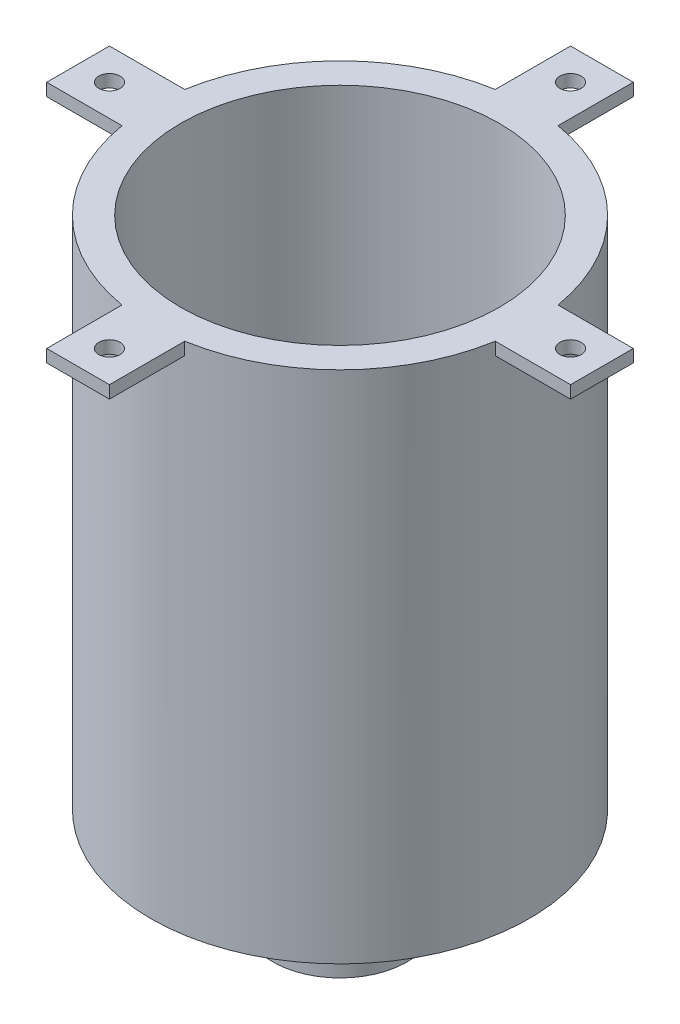
SolidWorks part; units mm, degrees
ref_plane "Front Plane" through (0, 0, 0) normal (0, 0, 1) x (1, 0, 0)
ref_plane "Top Plane" through (0, 0, 0) normal (0, 1, 0) x (1, 0, 0)
ref_plane "Right Plane" through (0, 0, 0) normal (1, 0, 0) x (0, 0, -1)
sketch "Sketch1" plane through (0, 0, 0) normal (0, 0, 1) x (1, 0, 0)
  line L0 (0, 0) -> (0, 47.7) construction
  line L1 (0, 47.7) -> (3.25, 47.7) construction
  line L2 (3.25, 47.7) -> (4.8, 47.7)
  line L3 (4.8, 47.7) -> (5.2, 43.2178)
  line L4 (5.2, 43.2178) -> (4.8, 42.5333)
  line L5 (4.8, 42.5333) -> (5.2, 38.0511)
  line L6 (5.2, 38.0511) -> (4.8, 37.3667)
  line L7 (4.8, 37.3667) -> (5.2, 32.8845)
  line L8 (5.2, 32.8845) -> (4.8, 32.2)
  line L9 (4.8, 32.2) -> (5.25, 26.2)
  line L10 (5.5, 0) -> (5.5, 18)
  line L11 (5.5, 18) -> (3.25, 19.7)
  line L12 (5.25, 26.2) -> (5.25, 22.2)
  line L13 (5.25, 22.2) -> (10.6, 22.2)
  line L14 (10.6, 22.2) -> (10.6, 15)
  line L15 (10.6, 15) -> (8.3, 15)
  line L16 (8.3, 15) -> (8.3, 0)
  line L17 (8.3, 0) -> (5.5, 0)
  line L18 (3.25, 19.7) -> (3.25, 47.7)
  dimension "D1" = 6.5
  dimension "D2" = 9.6
  dimension "D3" = 10.4
  dimension "D4" = 47.7
  dimension "D5" = 4.5
  dimension "D6" = 25.5
  dimension "D7" = 21.2
  dimension "D8" = 7.2
  dimension "D9" = 4
  dimension "D10" = 10.5
  dimension "D11" = 6
  dimension "D12" = 16.6
  dimension "D13" = 11
  dimension "D14" = 28
  dimension "D15" = 18
revolve "Revolve1" add sketch "Sketch1" angle 360 about L0
sketch "Sketch2" plane through (0, 0, 0) normal (0, 0, 1) x (1, 0, 0)
  line L0 (7.5, 0) -> (8.3, 0.4619)
  line L1 (8.3, 0) -> (5.5, 0) construction
  line L2 (8.3, 15) -> (8.3, 0) construction
  line L3 (8.3, 0.4619) -> (8.3, -0.4619)
  line L4 (8.3, -0.4619) -> (7.5, 0)
  line L5 (-7.5, 0) -> (7.5, 0) construction
  point P12 (0, 0)
  dimension "D1" = 15
sketch "Sketch3" plane through (0, 0, 0) normal (0, -1, 0) x (1, 0, 0)
  circle A0 centre (0, 0) radius 8.3 construction
  circle A1 centre (0, 0) radius 8.3
sketch "Sketch5" plane through (0, 22.2, 0) normal (0, 1, 0) x (1, 0, 0)
  line L0 (-5.3, 9.1799) -> (5.3, 9.1799)
  line L1 (5.3, 9.1799) -> (10.6, 0)
  line L2 (10.6, 0) -> (8.3, 0) construction
  line L3 (10.6, 0) -> (5.3, -9.1799)
  line L4 (5.3, -9.1799) -> (-5.3, -9.1799)
  line L5 (-5.3, -9.1799) -> (-10.6, 0)
  line L6 (-10.6, 0) -> (-5.3, 9.1799)
  circle A0 centre (0, 0) radius 10.6 construction
extrude "Cut-Extrude1" cut sketch "Sketch5" against normal up to surface (7.2 mm away) flip side to cut up to face at (0, 15, -10.6)
sketch "Sketch4" plane through (0, 0, 0) normal (0, 0, 1) x (1, 0, 0)
  line L0 (6.9, 0) -> (8.3, 1.4)
  line L1 (8.3, 0) -> (5.5, 0) construction
  line L2 (8.3, 15) -> (8.3, 0) construction
  line L3 (8.3, 1.4) -> (8.3, 0)
  line L4 (8.3, 0) -> (6.9, 0)
  line L5 (0, 0) -> (0, 15) construction
  line L6 (0, 0) -> (0, 47.7) construction
  line L7 (-8.3, 15) -> (8.3, 15) construction
  line L8 (0, 15) -> (8.3, 15) construction
  line L10 (8.3, 15) -> (10.6, 15.8371)
  line L11 (10.6, 22.2) -> (10.6, 15) construction
  line L12 (10.6, 15.8371) -> (10.6, 15)
  line L13 (10.6, 15) -> (8.3, 15)
  line L14 (8.3, 15) -> (8.3, 22.2) construction
  line L15 (5.25, 22.2) -> (10.6, 22.2) construction
  line L16 (8.3, 22.2) -> (10.6, 21.3629)
  line L17 (10.6, 21.3629) -> (10.6, 22.2)
  line L18 (10.6, 22.2) -> (8.3, 22.2)
  dimension "D1" = 45
  dimension "D2" = 20
revolve "Cut-Revolve1" cut sketch "Sketch4" angle 360 about L5
sketch "Sketch10" plane through (0, 0, 0) normal (0, -1, 0) x (1, 0, 0)
  circle A0 centre (0, 0) radius 10.705
  circle A3 centre (0, 0) radius 6.9 construction
  circle A4 centre (0, 0) radius 6.9
  dimension "D1" = 21.41
extrude "Boss-Extrude1" add sketch "Sketch10" against normal up to surface (15.8753 mm away) up to face at (0, 15.8371, 0)
sketch "Sketch11" plane through (0, 0, 0) normal (0, -1, 0) x (1, 0, 0)
  circle A0 centre (0, 0) radius 7.874
  circle A1 centre (0, 0) radius 5.5 construction
  circle A2 centre (0, 0) radius 5.5
  dimension "D1" = 15.748
extrude "Cut-Extrude2" cut sketch "Sketch11" against normal up to surface (16.2063 mm away) up to face at (0, 18, -5.5)
sketch "Sketch12" plane through (0, 22.2, 0) normal (0, 1, 0) x (1, 0, 0)
  line L0 (-7.6094, 13.1799) -> (-15.2188, 0)
  line L1 (-15.2188, 0) -> (-7.6094, -13.1799)
  line L2 (-7.6094, -13.1799) -> (7.6094, -13.1799)
  line L3 (7.6094, -13.1799) -> (15.2188, 0)
  line L4 (15.2188, 0) -> (7.6094, 13.1799)
  line L5 (7.6094, 13.1799) -> (-7.6094, 13.1799)
  line L6 (-5.3, 9.1799) -> (-10.6, 0)
  line L7 (-10.6, 0) -> (-5.3, -9.1799)
  line L8 (-5.3, -9.1799) -> (5.3, -9.1799)
  line L9 (5.3, -9.1799) -> (10.6, 0)
  line L10 (10.6, 0) -> (5.3, 9.1799)
  line L11 (5.3, 9.1799) -> (-5.3, 9.1799)
  line L12 (-5.3, 9.1799) -> (-10.6, 0) construction
  line L13 (-10.6, 0) -> (-5.3, -9.1799) construction
  line L14 (-5.3, -9.1799) -> (5.3, -9.1799) construction
  line L15 (5.3, -9.1799) -> (10.6, 0) construction
  line L16 (10.6, 0) -> (5.3, 9.1799) construction
  line L17 (5.3, 9.1799) -> (-5.3, 9.1799) construction
  circle A0 centre (0, 0) radius 8.3 construction
  circle A1 centre (0, 0) radius 8.3
  dimension "D1" = 0
  dimension "D2" = 4
extrude "Boss-Extrude3" add sketch "Sketch12" against normal up to surface (4.6818 mm away) up to face at (0, 15.8371, 0)
sketch "Sketch13" plane through (0, 47.7, 0) normal (0, 1, 0) x (1, 0, 0)
  circle A0 centre (0, 0) radius 3.45
  circle A1 centre (0, 0) radius 3.25 construction
  dimension "D1" = 0.2
extrude "Cut-Extrude3" cut sketch "Sketch13" against normal up to surface (28.1511 mm away)
sketch "Sketch14" plane through (0, 47.7, 0) normal (0, 1, 0) x (1, 0, 0)
  circle A0 centre (0, 0) radius 23.9795
extrude "Cut-Extrude5" cut sketch "Sketch14" against normal blind 32
sketch "Sketch16" plane through (0, 15.7, 0) normal (0, 1, 0) x (1, 0, 0)
  circle A0 centre (0, 0) radius 30.1625
  circle A1 centre (0, 0) radius 7.874 construction
  circle A2 centre (0, 0) radius 7.874
  dimension "D1" = 60.325
extrude "Boss-Extrude4" add sketch "Sketch16" along normal blind 2
sketch "Sketch17" plane through (0, 17.7, 0) normal (0, 1, 0) x (1, 0, 0)
  circle A0 centre (0, 0) radius 25.4
  circle A1 centre (0, 0) radius 30.1625
  circle A2 centre (0, 0) radius 30.1625
  dimension "D2" = 50.8
  dimension "D1" = 0
extrude "Boss-Extrude5" add sketch "Sketch17" along normal blind 80
sketch "Sketch18" plane through (0, 97.7, 0) normal (0, 1, 0) x (1, 0, 0)
  line L0 (-30.1625, 0) -> (0, 0) construction
  line L1 (0, 0) -> (30.1625, 0) construction
  line L2 (0, -30.1625) -> (0, 0) construction
  line L3 (0, 0) -> (0, 30.1625) construction
  line L4 (-29.7452, 5) -> (-29.7452, -5)
  line L5 (-29.7452, 5) -> (-41.7452, 5)
  line L6 (-29.7452, -5) -> (-41.7452, -5)
  line L7 (-41.7452, 5) -> (-41.7452, -5)
  line L8 (29.7452, 5) -> (29.7452, -5)
  line L9 (29.7452, 5) -> (41.7452, 5)
  line L10 (29.7452, -5) -> (41.7452, -5)
  line L11 (41.7452, 5) -> (41.7452, -5)
  line L12 (-5, -29.7452) -> (5, -29.7452)
  line L13 (-5, -29.7452) -> (-5, -41.7452)
  line L14 (5, -29.7452) -> (5, -41.7452)
  line L15 (-5, -41.7452) -> (5, -41.7452)
  line L16 (-5, 29.7452) -> (5, 29.7452)
  line L17 (-5, 29.7452) -> (-5, 41.7452)
  line L18 (5, 29.7452) -> (5, 41.7452)
  line L19 (-5, 41.7452) -> (5, 41.7452)
  line L20 (29.7452, 0) -> (36.7452, 0) construction
  line L21 (0, -36.7452) -> (0, -29.7452) construction
  line L22 (-36.7452, 0) -> (-29.7452, 0) construction
  line L23 (0, 29.7452) -> (0, 36.7452) construction
  arc A0 (29.7452, 5) -> (29.7452, -5) centre (0, 0) cw
  circle A1 centre (0, 0) radius 30.1625 construction
  arc A2 (-29.7452, 5) -> (-29.7452, -5) centre (0, 0) ccw
  arc A3 (-5, -29.7452) -> (5, -29.7452) centre (0, 0) ccw
  arc A4 (-5, 29.7452) -> (5, 29.7452) centre (0, 0) cw
  circle A5 centre (0, 36.7452) radius 1.7
  circle A6 centre (-36.7452, 0) radius 1.7
  circle A7 centre (0, -36.7452) radius 1.7
  circle A8 centre (36.7452, 0) radius 1.7
  circle M5 centre (0, 0) radius 30.1625
  dimension "D1" = 10
  dimension "D4" = 3.4
  dimension "D2" = 12
  dimension "D3" = 7
extrude "Boss-Extrude6" add sketch "Sketch18" against normal blind 2 contours L5 L7 L6 M5 | L13 L15 L14 M5 | L11 L9 L10 M5 | L19 L17 L18 M5 region at (-30.3187, 97.7, 0) region at (-4.8438, 97.7, -35.7452) region at (0, 97.7, 30.3187) region at (35.7452, 97.7, -4.8438)
